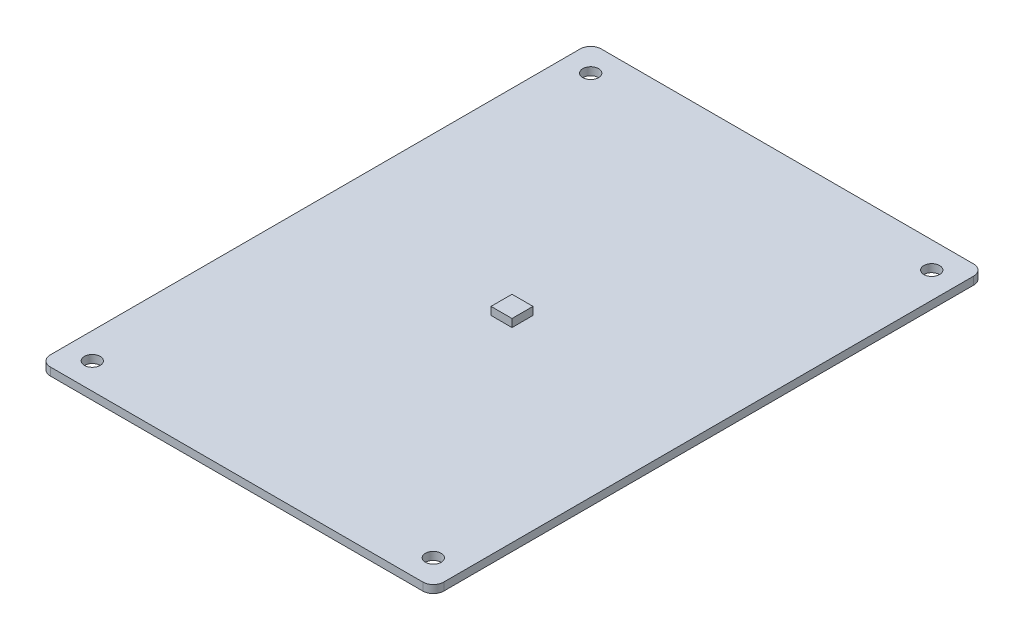
SolidWorks part; units mm, degrees
ref_plane "Plan de face" through (0, 0, 0) normal (0, 0, 1) x (1, 0, 0)
ref_plane "Plan de dessus" through (0, 0, 0) normal (0, 1, 0) x (1, 0, 0)
ref_plane "Plan de droite" through (0, 0, 0) normal (1, 0, 0) x (0, 0, -1)
sketch "Esquisse1" plane through (0, 0, 0) normal (0, 1, 0) x (1, 0, 0)
  line L0 (43.5142, -17.0401) -> (38.5142, -17.0401) construction
  line L1 (-29.4858, 82.9599) -> (41.5142, 82.9599)
  line L2 (-31.4858, 80.9599) -> (-31.4858, -20.0401)
  line L3 (-29.4858, -22.0401) -> (41.5142, -22.0401)
  line L4 (43.5142, 80.9599) -> (43.5142, -20.0401)
  line L5 (38.5142, -17.0401) -> (38.5142, -22.0401) construction
  line L6 (43.5142, 77.9599) -> (38.5142, 77.9599) construction
  line L7 (38.5142, 77.9599) -> (38.5142, 82.9599) construction
  line L8 (38.5142, 82.9599) -> (-26.4858, 82.9599) construction
  line L9 (-26.4858, 82.9599) -> (-26.4858, 77.9599) construction
  line L10 (-26.4858, 77.9599) -> (-31.4858, 77.9599) construction
  line L11 (-31.4858, 77.9599) -> (-31.4858, -17.0401) construction
  line L12 (-31.4858, -17.0401) -> (-26.4858, -17.0401) construction
  line L13 (-26.4858, -17.0401) -> (-26.4858, -22.0401) construction
  circle A0 centre (38.5142, 77.9599) radius 1.5
  circle A1 centre (38.5142, -17.0401) radius 1.5
  circle A2 centre (-26.4858, -17.0401) radius 1.5
  circle A3 centre (-26.4858, 77.9599) radius 1.5
  arc A4 (41.5142, -22.0401) -> (43.5142, -20.0401) centre (41.5142, -20.0401) ccw
  arc A5 (-31.4858, -20.0401) -> (-29.4858, -22.0401) centre (-29.4858, -20.0401) ccw
  arc A6 (-29.4858, 82.9599) -> (-31.4858, 80.9599) centre (-29.4858, 80.9599) ccw
  arc A7 (41.5142, 82.9599) -> (43.5142, 80.9599) centre (41.5142, 80.9599) cw
  point P22 (43.5142, -22.0401)
  point P27 (-31.4858, 82.9599)
  point P30 (43.5142, 82.9599)
  dimension "D3" = 2
  dimension "D1" = 75
  dimension "D2" = 105
extrude "Boss.-Extru.1" add sketch "Esquisse1" along normal blind 1.5
sketch "Esquisse2" plane through (0, 1.5, 0) normal (0, 1, 0) x (1, 0, 0)
  line L0 (43.5142, 30.4599) -> (-31.4858, 30.4599) construction
  line L1 (43.5142, -20.0401) -> (43.5142, 80.9599) construction
  line L2 (-31.4858, 80.9599) -> (-31.4858, -20.0401) construction
  line L3 (-31.4858, 30.4599) -> (6.0142, -22.0401) construction
  line L4 (-29.4858, -22.0401) -> (41.5142, -22.0401) construction
  line L5 (6.0142, -22.0401) -> (6.0142, 82.9599) construction
  line L6 (41.5142, 82.9599) -> (-29.4858, 82.9599) construction
  line L8 (4.0142, 32.4599) -> (8.0142, 32.4599)
  line L9 (4.0142, 32.4599) -> (4.0142, 28.4599)
  line L10 (4.0142, 28.4599) -> (8.0142, 28.4599)
  line L11 (8.0142, 32.4599) -> (8.0142, 28.4599)
  line L12 (4.0142, 32.4599) -> (8.0142, 28.4599) construction
  line L13 (4.0142, 28.4599) -> (8.0142, 32.4599) construction
  point P6 (6.0142, 30.4599)
  dimension "D1" = 4
  dimension "D2" = 4
extrude "Boss.-Extru.2" add sketch "Esquisse2" along normal blind 1.5
